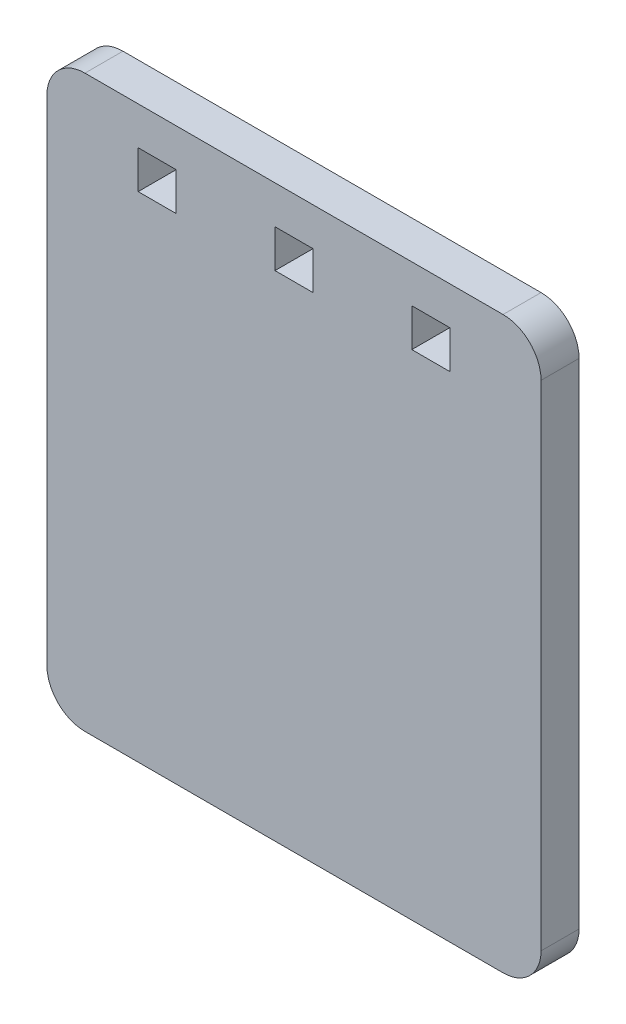
SolidWorks part; units mm, degrees
ref_plane "前视基准面" through (0, 0, 0) normal (0, 0, 1) x (1, 0, 0)
ref_plane "上视基准面" through (0, 0, 0) normal (0, 1, 0) x (1, 0, 0)
ref_plane "右视基准面" through (0, 0, 0) normal (1, 0, 0) x (0, 0, -1)
sketch "草图1" plane through (0, 0, 0) normal (0, 0, 1) x (1, 0, 0)
  line L1 (0, 0) -> (65, 0)
  line L2 (0, 0) -> (0, -75)
  line L3 (0, -75) -> (65, -75)
  line L4 (65, 0) -> (65, -75)
  dimension "D1" = 75
  dimension "D2" = 65
extrude "凸台-拉伸1" add sketch "草图1" along normal blind 5
sketch "草图2" plane through (0, 0, 5) normal (0, 0, 1) x (1, 0, 0)
  line L0 (0, 0) -> (0, -5) construction
  line L1 (0, 0) -> (0, -75) construction
  line L2 (0, -5) -> (65, -5) construction
  line L3 (65, -75) -> (65, 0) construction
  line L4 (65, -5) -> (65, -10) construction
  line L5 (65, -10) -> (0, -10) construction
  line L6 (0, -10) -> (0, -5) construction
  line L7 (0, -10) -> (12, -10) construction
  line L8 (12, -10) -> (12, -5)
  line L9 (12, -5) -> (17, -5)
  line L10 (17, -5) -> (17, -10)
  line L11 (17, -10) -> (12, -10)
  line L12 (32.5, -5) -> (30, -5)
  line L13 (30, -5) -> (30, -10)
  line L14 (30, -10) -> (35, -10)
  line L15 (35, -10) -> (35, -5)
  line L16 (35, -5) -> (32.5, -5)
  line L17 (65, -10) -> (53, -10)
  line L18 (53, -10) -> (53, -5)
  line L19 (53, -5) -> (48, -5)
  line L20 (48, -5) -> (48, -10)
  line L21 (48, -10) -> (53, -10)
  dimension "D1" = 5
  dimension "D2" = 5
  dimension "D3" = 12
  dimension "D4" = 5
  dimension "D5" = 2.5
  dimension "D6" = 5
  dimension "D7" = 12
  dimension "D8" = 5
extrude "切除-拉伸1" cut sketch "草图2" against normal blind 5 contours L15 L16 L12 L13 L14 | L20 L21 L18 L19 | L11 L10 L9 L8 region at (14.5, -7.5, 5) region at (32.5, -7.5, 5) region at (50.5, -7.5, 5)
fillet "圆角1" radius 5 4 edges at (0, -75, 2.5) (65, -75, 2.5) (65, 0, 2.5) (0, 0, 2.5)
